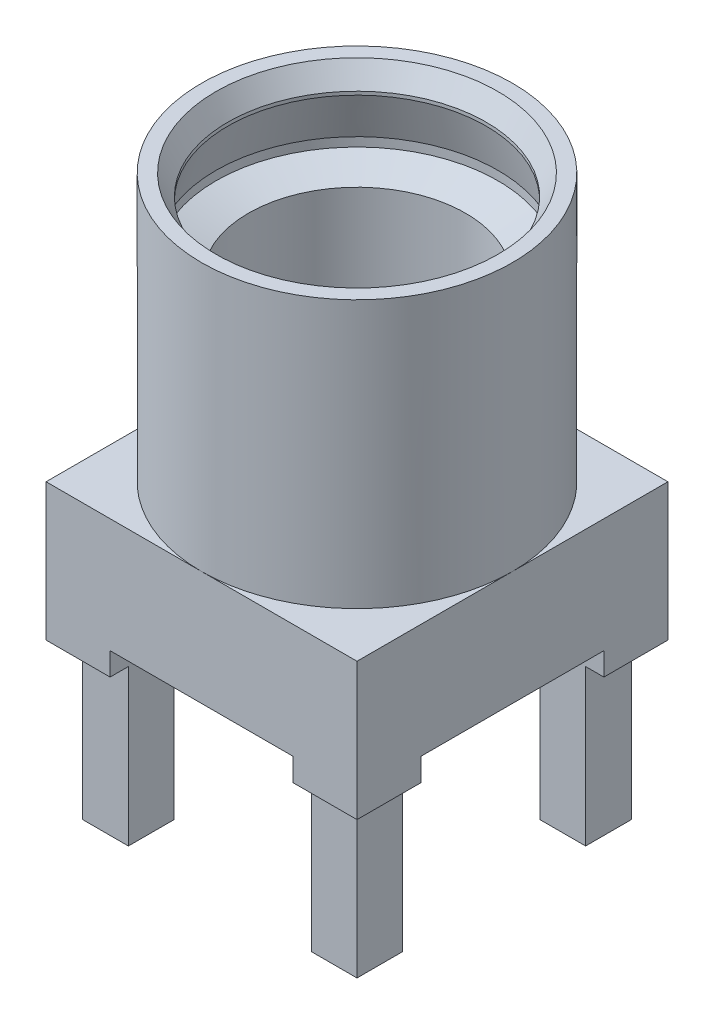
SolidWorks part; units mm, degrees
ref_plane "Front Plane" through (0, 0, 0) normal (0, 0, 1) x (1, 0, 0)
ref_plane "Top Plane" through (0, 0, 0) normal (0, 1, 0) x (1, 0, 0)
ref_plane "Right Plane" through (0, 0, 0) normal (1, 0, 0) x (0, 0, -1)
sketch "Sketch1" plane through (0, 0, 0) normal (0, 1, 0) x (1, 0, 0)
  line L1 (-1.7272, -1.7272) -> (1.7272, -1.7272)
  line L2 (-1.7272, -1.7272) -> (-1.7272, 1.7272)
  line L3 (-1.7272, 1.7272) -> (1.7272, 1.7272)
  line L4 (1.7272, -1.7272) -> (1.7272, 1.7272)
  line L5 (-1.7272, -1.7272) -> (1.7272, 1.7272) construction
  line L6 (-1.7272, 1.7272) -> (1.7272, -1.7272) construction
  point P0 (0, 0)
  dimension "D1" = 3.4544
extrude "Boss-Extrude1" add sketch "Sketch1" along normal blind 1.27
sketch "Sketch2" plane through (0, 0, 0) normal (0, -1, 0) x (1, 0, 0)
  line L0 (0, 1.7272) -> (0, -1.7272) construction
  line L1 (-1.7272, 1.7272) -> (-1.016, 1.7272)
  line L2 (-1.7272, 1.7272) -> (-1.7272, 1.016)
  line L3 (-1.7272, 1.016) -> (-1.016, 1.016)
  line L4 (-1.016, 1.7272) -> (-1.016, 1.016)
  line L5 (-1.7272, 1.7272) -> (1.7272, 1.7272) construction
  line L6 (1.7272, -1.7272) -> (-1.7272, -1.7272) construction
  line L7 (-1.7272, 0) -> (1.7272, 0) construction
  line L8 (-1.7272, -1.7272) -> (-1.7272, 1.7272) construction
  line L9 (1.7272, 1.7272) -> (1.7272, -1.7272) construction
  line L10 (1.016, 1.7272) -> (1.016, 1.016)
  line L11 (1.7272, 1.016) -> (1.016, 1.016)
  line L12 (1.7272, 1.7272) -> (1.7272, 1.016)
  line L13 (1.7272, 1.7272) -> (1.016, 1.7272)
  line L14 (1.7272, -1.7272) -> (1.016, -1.7272)
  line L15 (1.7272, -1.7272) -> (1.7272, -1.016)
  line L16 (1.7272, -1.016) -> (1.016, -1.016)
  line L17 (1.016, -1.7272) -> (1.016, -1.016)
  line L18 (-1.016, -1.7272) -> (-1.016, -1.016)
  line L19 (-1.7272, -1.016) -> (-1.016, -1.016)
  line L20 (-1.7272, -1.7272) -> (-1.7272, -1.016)
  line L21 (-1.7272, -1.7272) -> (-1.016, -1.7272)
  dimension "D1" = 2.032
extrude "Boss-Extrude2" add sketch "Sketch2" along normal blind 0.254
sketch "Sketch3" plane through (0, -0.254, 0) normal (0, -1, 0) x (1, 0, 0)
  line L0 (1.524, 1.524) -> (1.016, 1.524)
  line L1 (-1.524, 1.524) -> (-1.016, 1.524)
  line L2 (-1.524, 1.524) -> (-1.524, 1.016)
  line L3 (-1.524, 1.016) -> (-1.016, 1.016)
  line L4 (-1.016, 1.524) -> (-1.016, 1.016)
  line L5 (1.524, 1.524) -> (1.524, 1.016)
  line L6 (1.524, 1.016) -> (1.016, 1.016)
  line L7 (1.016, 1.524) -> (1.016, 1.016)
  line L8 (1.524, -1.524) -> (1.524, -1.016)
  line L9 (1.524, -1.524) -> (1.016, -1.524)
  line L10 (1.016, -1.524) -> (1.016, -1.016)
  line L11 (1.524, -1.016) -> (1.016, -1.016)
  line L12 (-1.524, -1.524) -> (-1.016, -1.524)
  line L13 (-1.524, -1.524) -> (-1.524, -1.016)
  line L14 (-1.524, -1.016) -> (-1.016, -1.016)
  line L15 (-1.016, -1.524) -> (-1.016, -1.016)
  point P5 (2.4514, 1.2186)
  point P6 (0, 0)
  point P7 (0, 0)
  point P20 (0, 0)
  point P22 (0, 0)
  point P24 (0, 0)
  point P25 (0, 0)
  dimension "D1" = 0.508
  dimension "D2" = 4
extrude "Boss-Extrude3" add sketch "Sketch3" along normal blind 1.7272
sketch "Sketch4" plane through (0, 1.27, 0) normal (0, 1, 0) x (1, 0, 0)
  line L0 (1.7272, 1.7272) -> (-1.7272, 1.7272) construction
  circle A0 centre (0, 0) radius 1.7272
  circle A1 centre (0, 0) radius 0.4572
  point P6 (0, 0)
  dimension "D1" = 1.27
extrude "Boss-Extrude4" add sketch "Sketch4" along normal offset from surface (2.9718 mm away) 4.4958 up to face at (-1.4224, -0.254, 1.4224)
sketch "Sketch5" plane through (0, 0, 0) normal (0, -1, 0) x (1, 0, 0)
  circle A0 centre (0, 0) radius 0.3556
  dimension "D1" = 0.7112
extrude "Boss-Extrude5" add sketch "Sketch5" along normal up to surface (1.9812 mm away) up to face at (-1.27, -1.9812, 1.27)
chamfer "Chamfer1" distance 0.0762 angle 45 1 edges at (0, -1.9812, -0.3556)
sketch "Sketch7" plane through (0, 0, 0) normal (0, 0, 1) x (1, 0, 0)
  line L0 (0, 1.651) -> (0, 4.2418)
  line L1 (1.7272, 4.2418) -> (-1.7272, 4.2418) construction
  line L2 (0, 4.2418) -> (1.5671, 4.2418)
  line L3 (1.5671, 4.2418) -> (1.4351, 4.0132)
  line L4 (1.4351, 4.0132) -> (1.4351, 3.9751)
  line L5 (1.4351, 3.9751) -> (1.5671, 3.4825)
  line L6 (1.5671, 3.4825) -> (1.5671, 3.3824)
  line L7 (1.5671, 3.3824) -> (1.2065, 3.2512)
  line L8 (1.2065, 3.2512) -> (1.2065, 1.651)
  line L10 (1.2065, 1.651) -> (0, 1.651)
  point P0 (1.5146, 2.9715)
  dimension "D1" = 30
  dimension "D2" = 15
  dimension "D3" = 0.2286
  dimension "D4" = 2.3241
  dimension "D5" = 1.6002
  dimension "D6" = 1.4351
  dimension "D7" = 1.2065
  dimension "D8" = 70
  dimension "D9" = 2.5908
revolve "Cut-Revolve1" cut sketch "Sketch7" angle 360 about L0
sketch "Sketch9" plane through (0, 0, 0) normal (0, 0, 1) x (1, 0, 0)
  line L0 (0, 1.27) -> (0, 2.3604) construction
  line L1 (0.4572, 1.27) -> (-0.4572, 1.27) construction
  line L2 (0, 2.6726) -> (0.2032, 1.651)
  line L4 (0.3068, 1.651) -> (0.0997, 2.6924)
  line L5 (0.0997, 2.6924) -> (0, 2.6726)
  line L6 (1.2065, 1.651) -> (-1.2065, 1.651) construction
  line L8 (0.2032, 1.651) -> (0, 1.651)
  line L9 (0.3068, 1.651) -> (0.3068, 1.27)
  line L10 (0.3068, 1.27) -> (0, 1.27)
  line L11 (0, 1.651) -> (0, 1.27)
  point P3 (0, 0)
  dimension "D1" = 1.0414
  dimension "D2" = 0.4064
  dimension "D3" = 0
  dimension "D4" = 0.1016
revolve "Revolve2" add sketch "Sketch9" angle 360 about L0
sketch "Sketch11" plane through (0, 0, 0) normal (0, 0, 1) x (1, 0, 0)
  line L0 (0.2032, 1.651) -> (-0.2032, 1.651) construction
  line L1 (0, 1.651) -> (0.3302, 1.651)
  line L6 (0, 1.651) -> (0, 2.794)
  line L13 (0, 2.794) -> (0.3302, 2.794)
  line L14 (0.3302, 1.651) -> (0.3302, 2.794)
  point P4 (0, 0)
  dimension "D1" = 1.143
  dimension "D2" = 0.3302
revolve "Cut-Revolve4" cut sketch "Sketch11" angle 45 about L6
pattern_circular "CirPattern1" count 4 over 360 about axis through (0, 1.27, 0) along (0, 1, 0) of "Cut-Revolve4"
